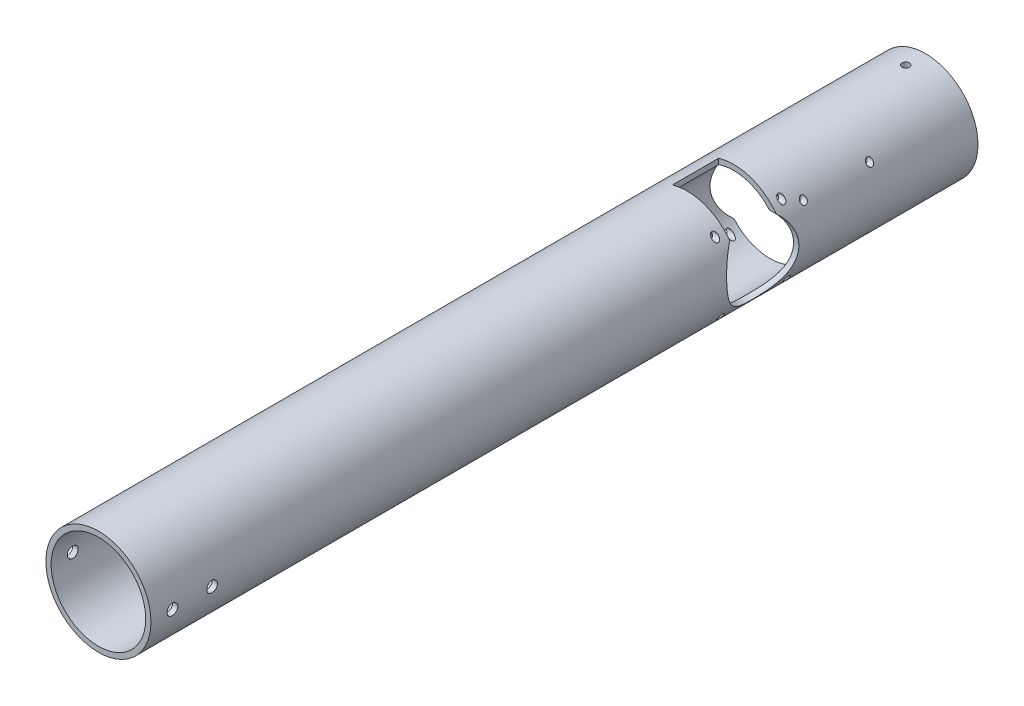
SolidWorks part; units mm, degrees
ref_plane "Front Plane" through (0, 0, 0) normal (0, 0, 1) x (1, 0, 0)
ref_plane "Top Plane" through (0, 0, 0) normal (0, 1, 0) x (1, 0, 0)
ref_plane "Right Plane" through (0, 0, 0) normal (1, 0, 0) x (0, 0, -1)
sketch "Sketch1" plane through (0, 0, 0) normal (0, 0, 1) x (1, 0, 0)
  circle A0 centre (0, 0) radius 31.75
  circle A1 centre (0, 0) radius 28.575
  dimension "D1" = 63.5
  dimension "D2" = 57.15
extrude "Boss-Extrude1" add sketch "Sketch1" along normal blind 250 and the other way blind 250 contours A1 | A0 region at (0, 0, 0)
sketch "Sketch2" plane through (0, 0, 0) normal (1, 0, 0) x (0, 0, -1)
  circle A2 centre (170, -2) radius 21.75
  dimension "D1" = 43.5
  dimension "D2" = 170
  dimension "D3" = 2
extrude "Cut-Extrude1" cut sketch "Sketch2" against normal through all
sketch "Sketch3" plane through (0, 0, 0) normal (1, 0, 0) x (0, 0, -1)
  circle A1 centre (120, 2) radius 21.75
  dimension "D1" = 120
  dimension "D2" = 43.5
  dimension "D3" = 2
extrude "Cut-Extrude2" cut sketch "Sketch3" along normal through all
sketch "Sketch5" plane through (0, 0, 0) normal (1, 0, 0) x (0, 0, -1)
  line L1 (184, -12.75) -> (156, -12.75)
  line L2 (184, -12.75) -> (184, -34.75)
  line L3 (184, -34.75) -> (156, -34.75)
  line L4 (156, -12.75) -> (156, -34.75)
  line L5 (184, -12.75) -> (156, -34.75) construction
  line L6 (184, -34.75) -> (156, -12.75) construction
  circle A0 centre (170, -2) radius 21.75 construction
  circle A1 centre (170, -2) radius 21.75 construction
  point P0 (170, -23.75)
  dimension "D1" = 28
  dimension "D2" = 22
  dimension "D3" = 170
extrude "Cut-Extrude4" cut sketch "Sketch5" against normal through all from offset 9
sketch "Sketch6" plane through (0, 0, 0) normal (1, 0, 0) x (0, 0, -1)
  line L1 (106, 34.75) -> (134, 34.75)
  line L2 (106, 34.75) -> (106, 12.75)
  line L3 (106, 12.75) -> (134, 12.75)
  line L4 (134, 34.75) -> (134, 12.75)
  line L5 (106, 34.75) -> (134, 12.75) construction
  line L6 (106, 12.75) -> (134, 34.75) construction
  circle A0 centre (120, 2) radius 21.75 construction
  circle A1 centre (120, 2) radius 21.75 construction
  point P0 (120, 23.75)
  dimension "D1" = 28
  dimension "D2" = 22
  dimension "D3" = 120
extrude "Cut-Extrude5" cut sketch "Sketch6" along normal through all from offset 9 offset against normal yes
sketch "Sketch10" plane through (0, 0, 0) normal (1, 0, 0) x (0, 0, -1)
  line L1 (210, 38) -> (130, 38)
  line L2 (210, 38) -> (210, -42)
  line L3 (210, -42) -> (130, -42)
  line L4 (130, 38) -> (130, -42)
  line L5 (210, 38) -> (130, -42) construction
  line L6 (210, -42) -> (130, 38) construction
  point P0 (170, -2)
  dimension "D1" = 80
  dimension "D2" = 80
sketch "Sketch11" plane through (0, 0, 0) normal (1, 0, 0) x (0, 0, -1)
  line L0 (210, 38) -> (130, -42) construction
  line L1 (210, -42) -> (130, 38) construction
  circle A0 centre (190, 18) radius 2
  circle A1 centre (150, 18) radius 2
  circle A2 centre (150, -22) radius 2
  circle A3 centre (190, -22) radius 2
  dimension "D5" = 4
  dimension "D6" = 4
  dimension "D7" = 4
  dimension "D8" = 4
  dimension "D1" = 20
  dimension "D2" = 20
  dimension "D3" = 20
  dimension "D4" = 20
extrude "Cut-Extrude8" cut sketch "Sketch11" against normal through all both and the other way through all
sketch "Sketch12" plane through (0, 0, 0) normal (1, 0, 0) x (0, 0, -1)
  line L1 (-250, 31.75) -> (-250, -31.75) construction
  circle A0 centre (-213, 0) radius 3.25
  circle A1 centre (-237, 0) radius 3.25
  dimension "D1" = 6.5
  dimension "D2" = 6.5
  dimension "D3" = 24
  dimension "D4" = 13
extrude "Cut-Extrude10" cut sketch "Sketch12" against normal through all both and the other way through all
sketch "Sketch13" plane through (0, 0, 0) normal (0, 1, 0) x (1, 0, 0)
  line L0 (0, -44) -> (0, 44) construction
  line L1 (28.575, 250) -> (-28.575, 250) construction
  circle A0 centre (0, 238) radius 2.25
  dimension "D2" = 4.5
  dimension "D1" = 12
extrude "Cut-Extrude11" cut sketch "Sketch13" against normal through all both and the other way through all
sketch "Sketch14" plane through (0, 0, 0) normal (1, 0, 0) x (0, 0, -1)
  line L1 (95, 27) -> (145, 27)
  line L2 (95, 27) -> (95, -23)
  line L3 (95, -23) -> (145, -23)
  line L4 (145, 27) -> (145, -23)
  line L5 (95, 27) -> (145, -23) construction
  line L6 (95, -23) -> (145, 27) construction
  circle A0 centre (100, 22) radius 2
  circle A1 centre (140, 22) radius 2
  circle A2 centre (140, -18) radius 2
  circle A3 centre (100, -18) radius 2
  point P0 (120, 2)
  point P14 (0, 0)
  point P15 (0, 0)
  point P16 (100.7337, 17.8233)
  point P19 (124.6363, 4.2784)
  dimension "D4" = 4
  dimension "D5" = 4
  dimension "D6" = 4
  dimension "D7" = 4
  dimension "D1" = 50
  dimension "D2" = 50
  dimension "D3" = 20
  dimension "D8" = 20
  dimension "D9" = 20
  dimension "D10" = 20
sketch "Sketch15" plane through (0, 0, 0) normal (1, 0, 0) x (0, 0, -1)
  circle A0 centre (100, 22) radius 2
  circle A1 centre (140, 22) radius 2
  circle A2 centre (140, -18) radius 2
  circle A3 centre (100, -18) radius 2
extrude "Cut-Extrude12" cut sketch "Sketch15" against normal through all and the other way through all
